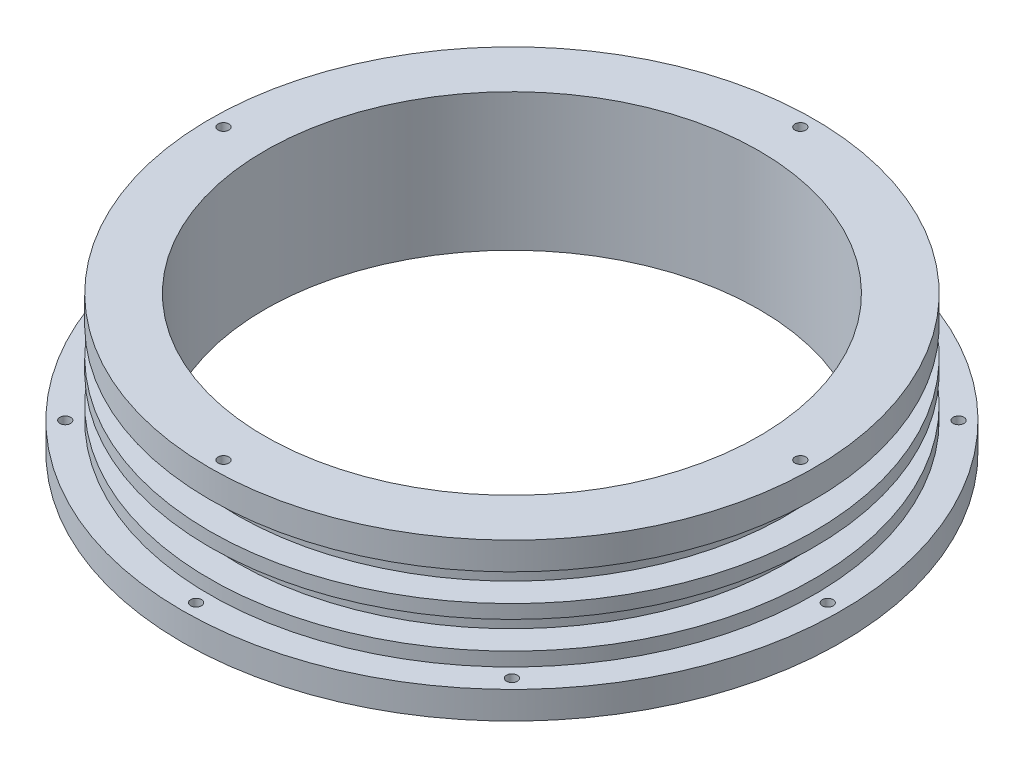
SolidWorks part; units mm, degrees
material "6061 Alloy"
ref_plane "Front Plane" through (0, 0, 0) normal (0, 0, 1) x (1, 0, 0)
ref_plane "Top Plane" through (0, 0, 0) normal (0, 1, 0) x (1, 0, 0)
ref_plane "Right Plane" through (0, 0, 0) normal (1, 0, 0) x (0, 0, -1)
sketch "Sketch2" plane through (0, 0, 0) normal (0, 1, 0) x (1, 0, 0)
  circle A0 centre (0, 0) radius 76.2
extrude "Boss-Extrude1" add sketch "Sketch2" along normal blind 6.35
sketch "Sketch3" plane through (0, 0, 0) normal (0, 1, 0) x (1, 0, 0)
  circle A0 centre (0, 0) radius 69.85
extrude "Boss-Extrude2" add sketch "Sketch3" along normal blind 9.525
sketch "Sketch4" plane through (0, 0, 0) normal (0, 1, 0) x (1, 0, 0)
  circle A0 centre (0, 0) radius 63.5
extrude "Boss-Extrude3" add sketch "Sketch4" along normal blind 15.875
sketch "Sketch6" plane through (0, 15.875, 0) normal (0, 1, 0) x (1, 0, 0)
  circle A0 centre (0, 0) radius 69.85
extrude "Boss-Extrude4" add sketch "Sketch6" along normal blind 3.175
sketch "Sketch7" plane through (0, 19.05, 0) normal (0, 1, 0) x (1, 0, 0)
  circle A0 centre (0, 0) radius 63.5
extrude "Boss-Extrude5" add sketch "Sketch7" along normal blind 6.35
sketch "Sketch8" plane through (0, 25.4, 0) normal (0, 1, 0) x (1, 0, 0)
  circle A0 centre (0, 0) radius 69.85
extrude "Boss-Extrude6" add sketch "Sketch8" along normal blind 6.35
sketch "Sketch9" plane through (0, 0, 0) normal (0, -1, 0) x (1, 0, 0)
  circle A0 centre (0, 0) radius 57.15
extrude "Cut-Extrude1" cut sketch "Sketch9" against normal through all
sketch "Sketch10" plane through (0, 6.35, 0) normal (0, 1, 0) x (1, 0, 0)
  circle A0 centre (0, 73.025) radius 1.2497
  circle A1 centre (51.6365, 51.6365) radius 1.2497
  circle A2 centre (73.025, 0) radius 1.2497
  circle A3 centre (51.6365, -51.6365) radius 1.2497
  circle A4 centre (0, -73.025) radius 1.2497
  circle A5 centre (-51.6365, -51.6365) radius 1.2497
  circle A6 centre (-73.025, 0) radius 1.2497
  circle A7 centre (-51.6365, 51.6365) radius 1.2497
  point P19 (0, 0)
  dimension "D1" = 8
extrude "Cut-Extrude2" cut sketch "Sketch10" against normal through all
sketch "Sketch11" plane through (0, 0, 0) normal (0, -1, 0) x (1, 0, 0)
  circle A0 centre (0, 0) radius 63.5
  circle A1 centre (0, 0) radius 69.85
extrude "Cut-Extrude3" cut sketch "Sketch11" against normal blind 3.175
sketch "Sketch12" plane through (0, 31.75, 0) normal (0, 1, 0) x (1, 0, 0)
  circle A0 centre (0, -66.675) radius 1.2497
  circle A1 centre (-66.675, 0) radius 1.2497
  circle A2 centre (0, 66.675) radius 1.2497
  circle A3 centre (66.675, 0) radius 1.2497
  point P11 (0, 0)
  dimension "D1" = 4
extrude "Cut-Extrude4" cut sketch "Sketch12" against normal blind 3.175
